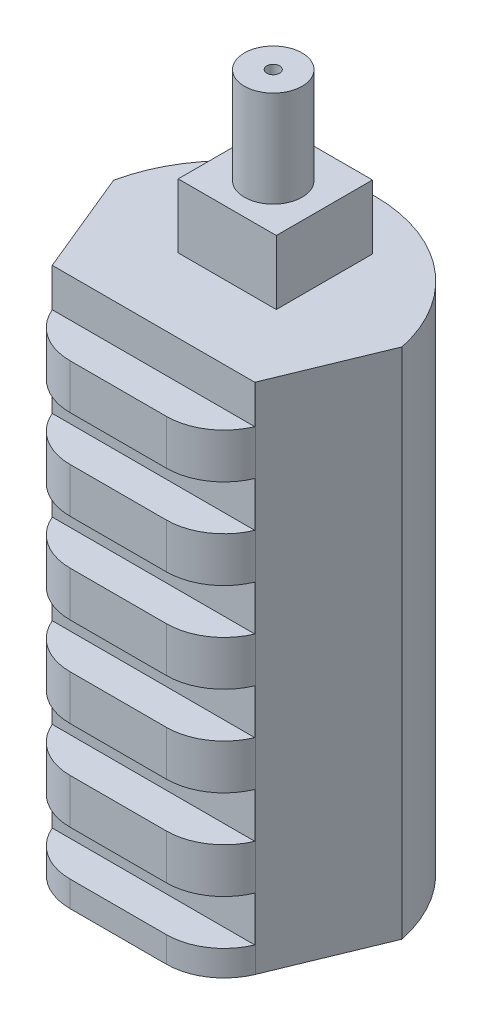
SolidWorks part; units mm, degrees
ref_plane "Front Plane" through (0, 0, 0) normal (0, 0, 1) x (1, 0, 0)
ref_plane "Top Plane" through (0, 0, 0) normal (0, 1, 0) x (1, 0, 0)
ref_plane "Right Plane" through (0, 0, 0) normal (1, 0, 0) x (0, 0, -1)
sketch "Sketch1" plane through (0, 0, 0) normal (0, 1, 0) x (1, 0, 0)
  line L6 (0, 0) -> (0, 20) construction
  line L7 (0, 0) -> (18.5832, 0) construction
  line L8 (0, 0) -> (-18.5832, 0) construction
  line L13 (7.5, -20) -> (-7.5, -20)
  line L14 (0, 0) -> (0, -20) construction
  line L22 (-7.5, -13) -> (7.5, -13)
  line L25 (22.5, 1.7697) -> (15.8205, -14.4306)
  line L26 (-22.5, 1.7697) -> (-15.8205, -14.4306)
  line L29 (-15.0674, -6.0103) -> (-13.9715, -8.6682)
  line L30 (13.9715, -8.6682) -> (15.0674, -6.0103)
  arc A1 (-22.5, 1.7697) -> (0, 20) centre (0, -3) cw
  arc A2 (0, 20) -> (22.5, 1.7697) centre (0, -3) cw
  arc A25 (15.8205, -14.4306) -> (7.5, -20) centre (7.5, -11) cw
  arc A26 (-15.8205, -14.4306) -> (-7.5, -20) centre (-7.5, -11) ccw
  arc A27 (-15.0674, -6.0103) -> (15.0674, -6.0103) centre (0, 0.2021) cw
  arc A28 (-7.5, -13) -> (-13.9715, -8.6682) centre (-7.5, -6) cw
  arc A30 (7.5, -13) -> (13.9715, -8.6682) centre (7.5, -6) ccw
  point P30 (0, -16.0958)
  point P32 (0, 16.5)
  point P42 (0, -20)
  dimension "D1" = 15
  dimension "D3" = 9
  dimension "D5" = 40
  dimension "D2" = 23
  dimension "D4" = 45
  dimension "D9" = 7
  dimension "D6" = 20
  dimension "D12" = 7
  dimension "D8" = 3.5
  dimension "D7" = 22.5
extrude "Boss-Extrude1" add sketch "Sketch1" along normal blind 80
extrude "Boss-Extrude2" add sketch "Sketch1<2>" along normal blind 5 contours A27 L22 region at (0, 0, -0.8924)
sketch "Sketch1<2>" plane through (0, 0, 0) normal (0, 1, 0) x (1, 0, 0) same geometry as "Sketch1"
extrude "Boss-Extrude3" add sketch "Sketch1<3>" against normal blind 5 from surface contours A27 L22 region at (0, 0, -0.8924) starting at face at (0, 80, 8.2699)
sketch "Sketch1<3>" plane through (0, 0, 0) normal (0, 1, 0) x (1, 0, 0) same geometry as "Sketch1"
sketch "Sketch2" plane through (0, 0, 0) normal (0, 0, 1) x (1, 0, 0)
  line L0 (-15.8205, 67) -> (15.8205, 67)
  line L1 (-22.5, 80) -> (22.5, 80)
  line L2 (-22.5, 80) -> (-22.5, 0)
  line L3 (-22.5, 0) -> (22.5, 0)
  line L4 (22.5, 80) -> (22.5, 0)
  line L5 (-15.8205, 80) -> (15.8205, 80)
  line L6 (-15.8205, 80) -> (-15.8205, 0)
  line L7 (-15.8205, 0) -> (15.8205, 0)
  line L8 (15.8205, 80) -> (15.8205, 0)
  line L9 (-15.8205, 74) -> (15.8205, 74)
  line L10 (-15.8205, 74) -> (-15.8205, 4)
  line L12 (15.8205, 74) -> (15.8205, 4)
  line L13 (-15.8205, 60) -> (15.8205, 60)
  line L14 (-15.8205, 53) -> (15.8205, 53)
  line L15 (-15.8205, 46) -> (15.8205, 46)
  line L16 (-15.8205, 39) -> (15.8205, 39)
  line L17 (-15.8205, 32) -> (15.8205, 32)
  line L18 (-15.8205, 25) -> (15.8205, 25)
  line L19 (15.8205, 0) -> (22.5, 0) construction
  line L20 (-15.8205, 4) -> (15.8205, 4)
  line L21 (-15.8205, 0) -> (15.8205, 0)
  line L22 (-22.5, 80) -> (-15.8205, 80) construction
  line L23 (-15.8205, 18) -> (15.8205, 18)
  line L24 (7.5, 0) -> (15.8205, 0) construction
  line L25 (-15.8205, 11) -> (15.8205, 11)
  line L26 (-15.8205, 0) -> (15.8205, 0)
  dimension "D2" = 7
  dimension "D3" = 7
  dimension "D4" = 7
  dimension "D5" = 7
  dimension "D6" = 7
  dimension "D7" = 7
  dimension "D8" = 7
  dimension "D9" = 4
  dimension "D13" = 7
  dimension "D14" = 7
  dimension "D15" = 7
extrude "Cut-Extrude1" cut sketch "Sketch2" against normal blind 5.5 from surface contours L25 L6 L20 L8 | L6 L23 L8 L18 | L6 L17 L8 L16 | L6 L15 L8 L14 | L6 L13 L8 L0 | L6 L9 L8 L1 region at (0, 63.5, 0) region at (0, 77, 0) region at (0, 49.5, 0) region at (0, 35.5, 0) region at (0, 7.5, 0) region at (0, 21.5, 0) starting at face at (0, 40, 20)
sketch "Croquis1" plane through (0, 80, 0) normal (0, 1, 0) x (1, 0, 0)
  line L0 (-7.5, -20) -> (7.5, -20) construction
  line L1 (-7.65, 12) -> (7.65, 12)
  line L2 (-7.65, 12) -> (-7.65, -3)
  line L3 (-7.65, -3) -> (7.65, -3)
  line L4 (7.65, 12) -> (7.65, -3)
  point P6 (0, -3)
  dimension "D1" = 32
  dimension "D2" = 15
  dimension "D3" = 15.3
extrude "Saliente-Extruir1" add sketch "Croquis1" along normal blind 10
sketch "Croquis2" plane through (0, 90, 0) normal (0, 1, 0) x (1, 0, 0)
  circle A0 centre (0, 4.1728) radius 1
  circle A1 centre (0, 4.1728) radius 4.5
  dimension "D1" = 9
  dimension "D2" = 2
extrude "Saliente-Extruir2" add sketch "Croquis2" along normal blind 15
extrude "Cortar-Extruir1" cut sketch "Croquis2<2>" against normal blind 24 contours A0 region at (0, 90, -4.1728)
sketch "Croquis2<2>" plane through (0, 90, 0) normal (0, 1, 0) x (1, 0, 0) same geometry as "Croquis2"
